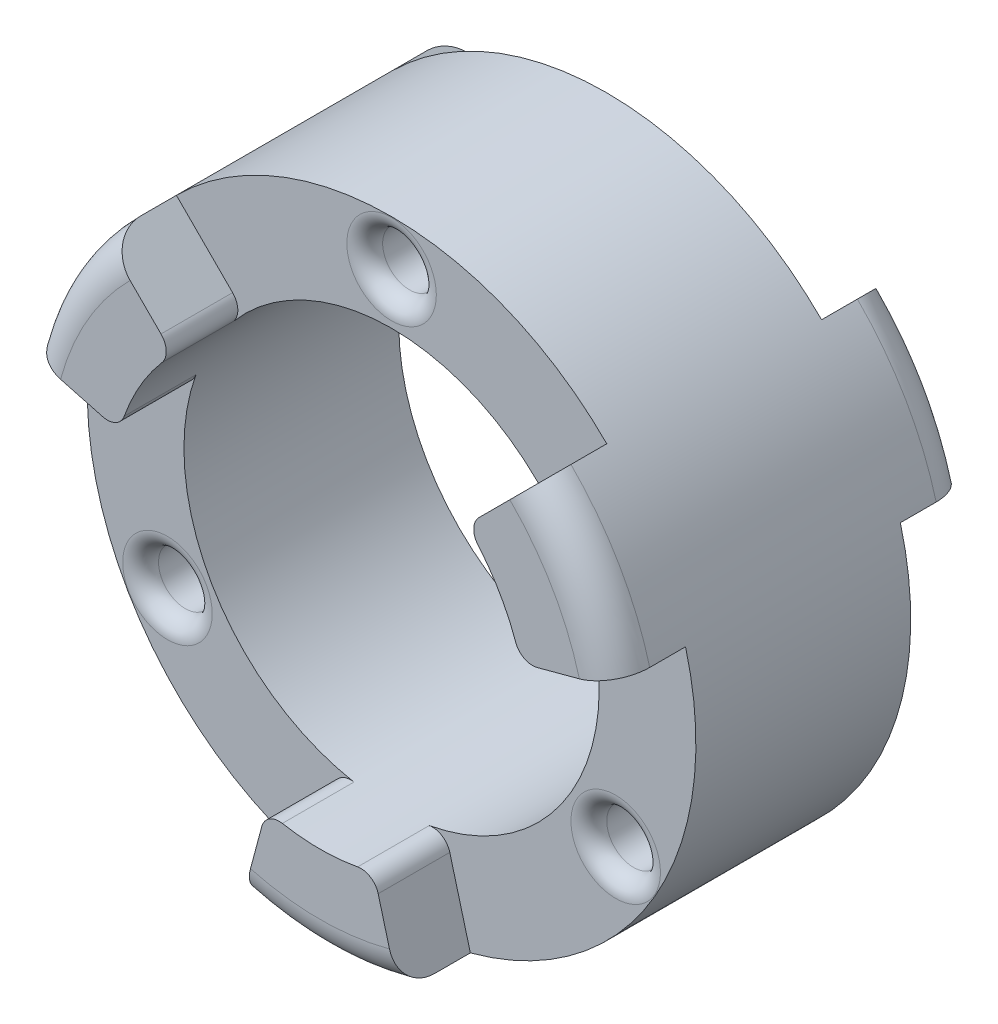
SolidWorks part; units mm, degrees
material "PET"
ref_plane "Front Plane" through (0, 0, 0) normal (0, 0, 1) x (1, 0, 0)
ref_plane "Top Plane" through (0, 0, 0) normal (0, 1, 0) x (1, 0, 0)
ref_plane "Right Plane" through (0, 0, 0) normal (1, 0, 0) x (0, 0, -1)
sketch "Sketch1" plane through (0, 0, 0) normal (0, 0, 1) x (1, 0, 0)
  line L0 (0, 0) -> (0, 2.9) construction
  line L1 (0, 3.239) -> (0, 3.614) construction
  line L2 (0, 3.239) -> (0, 2.9) construction
  circle A0 centre (0, 0) radius 2.9
  circle A1 centre (0, 0) radius 4.25
  circle A2 centre (0, 3.614) radius 0.375
  circle A3 centre (3.1298, -1.807) radius 0.375
  circle A4 centre (-3.1298, -1.807) radius 0.375
  point P15 (0, 0)
  dimension "D1" = 5.8
  dimension "D2" = 0.75
  dimension "D4" = 8.5
  dimension "D3" = 0.339
  dimension "D5" = 3
extrude "Boss-Extrude1" add sketch "Sketch1" along normal blind 3
sketch "Sketch2" plane through (0, 0, 3) normal (0, 0, 1) x (1, 0, 0)
  line L0 (-0.7506, -2.8012) -> (-1.1, -4.1052)
  line L1 (0, 0) -> (0, -4.001) construction
  line L2 (0.7506, -2.8012) -> (1.1, -4.1052)
  line L3 (-2.0506, 2.0506) -> (-3.0052, 3.0052)
  line L4 (-2.8012, 0.7506) -> (-4.1052, 1.1)
  line L5 (2.8012, 0.7506) -> (4.1052, 1.1)
  line L6 (2.0506, 2.0506) -> (3.0052, 3.0052)
  circle A0 centre (0, 0) radius 4.25 construction
  arc A1 (-1.1, -4.1052) -> (1.1, -4.1052) centre (0, 0) ccw
  arc A3 (-0.7506, -2.8012) -> (0.7506, -2.8012) centre (0, 0) ccw
  circle A4 centre (0, 0) radius 2.9 construction
  arc A5 (-3.0052, 3.0052) -> (-4.1052, 1.1) centre (0, 0) ccw
  arc A6 (-2.0506, 2.0506) -> (-2.8012, 0.7506) centre (0, 0) ccw
  arc A7 (4.1052, 1.1) -> (3.0052, 3.0052) centre (0, 0) ccw
  arc A8 (2.8012, 0.7506) -> (2.0506, 2.0506) centre (0, 0) ccw
  point P20 (0, 0)
  dimension "D1" = 15
  dimension "D2" = 3
extrude "Boss-Extrude2" add sketch "Sketch2" along normal blind 1 and the other way blind 4
fillet "Fillet1" radius 0.5 6 edges at (0, -4.25, -1) (-3.6806, 2.125, -1) (3.6806, 2.125, -1) (-3.6806, 2.125, 4) (0, -4.25, 4) (3.6806, 2.125, 4)
fillet "Fillet2" radius 0.25 6 edges at (0.375, 3.614, 0) (0.375, 3.614, 3) (3.5048, -1.807, 0) (3.5048, -1.807, 3) (-2.7548, -1.807, 0) (-2.7548, -1.807, 3)
fillet "Fillet3" radius 0.25 12 edges at (-2.8012, 0.7506, -0.5) (2.8012, 0.7506, -0.5) (0.7506, -2.8012, -0.5) (-0.7506, -2.8012, -0.5) (0.7506, -2.8012, 3.5) (-0.7506, -2.8012, 3.5) (-2.0506, 2.0506, -0.5) (2.0506, 2.0506, -0.5) (2.0506, 2.0506, 3.5) (2.8012, 0.7506, 3.5) (-2.0506, 2.0506, 3.5) (-2.8012, 0.7506, 3.5)
